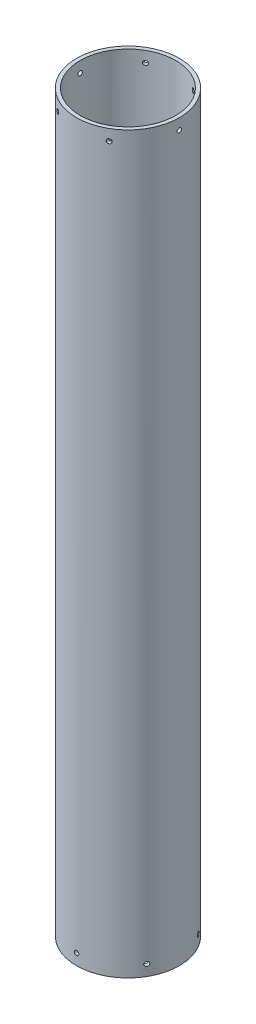
SolidWorks part; units mm, degrees
ref_plane "Front Plane" through (0, 0, 0) normal (0, 0, 1) x (1, 0, 0)
ref_plane "Top Plane" through (0, 0, 0) normal (0, 1, 0) x (1, 0, 0)
ref_plane "Right Plane" through (0, 0, 0) normal (1, 0, 0) x (0, 0, -1)
sketch "Sketch1" plane through (0, 0, 0) normal (0, 1, 0) x (1, 0, 0)
  line L0 (0, 0) -> (-6412.266, 0) construction
  line L1 (0, 0) -> (0, 8725.9702) construction
  circle A0 centre (0, 0) radius 70
  circle A1 centre (0, 0) radius 65
  dimension "D1" = 140
  dimension "D2" = 130
extrude "Boss-Extrude1" add sketch "Sketch1" along normal blind 1000
sketch "Sketch2" plane through (0, 0, 0) normal (1, 0, 0) x (0, 0, -1)
  line L0 (0, 800) -> (0, 720.2322) construction
  line L2 (65, 1000) -> (-65, 1000) construction
  circle A1 centre (0, 985) radius 3.05
  dimension "D1" = 6.1
  dimension "D2" = 15
extrude "Cut-Extrude1" cut sketch "Sketch2" against normal up to next contours A1
pattern_circular "CirPattern1" count 6 every 60 about axis through (0, 1000, 0) along (0, 1, 0) of "Cut-Extrude1"
sketch "Sketch3" plane through (0, 0, 0) normal (0, 0, 1) x (1, 0, 0)
  line L0 (0, 1000) -> (0, 0) construction
  line L1 (-65, 0) -> (65, 0) construction
  circle A0 centre (0, 15) radius 3.05
  point P6 (0, 0)
  dimension "D2" = 6.1
  dimension "D1" = 15
extrude "Cut-Extrude2" cut sketch "Sketch3" against normal through all
pattern_circular "CirPattern2" count 6 every 60 about axis through (0, 0, 0) along (0, 1, 0) of "Cut-Extrude2"
equation "\"th\"= 10"
equation "\"D2@Sketch1\"=\"D1@Sketch1\"-\"th\""
